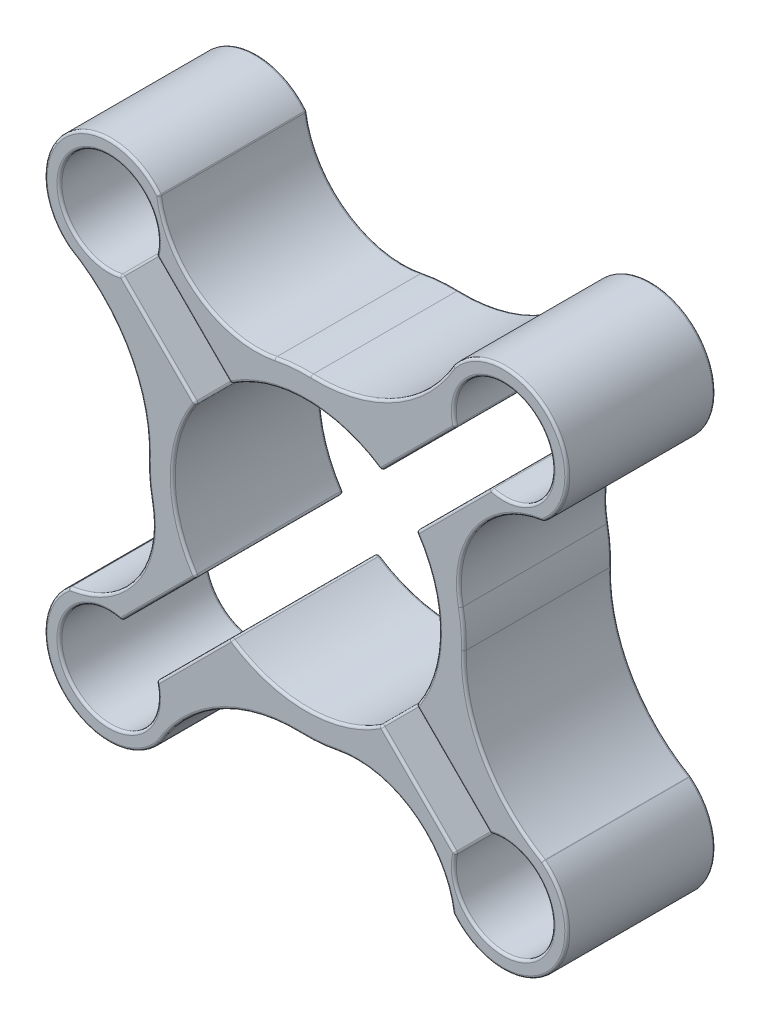
SolidWorks part; units mm, degrees
ref_plane "Front Plane" through (0, 0, 0) normal (0, 0, 1) x (1, 0, 0)
ref_plane "Top Plane" through (0, 0, 0) normal (0, 1, 0) x (1, 0, 0)
ref_plane "Right Plane" through (0, 0, 0) normal (1, 0, 0) x (0, 0, -1)
sketch "Sketch1" plane through (0, 0, 0) normal (0, 0, 1) x (1, 0, 0)
  line L0 (0, 0) -> (0, -51885.6815) construction
  line L1 (0, 0) -> (-51885.6815, 0) construction
  line L2 (707.1068, 707.1068) -> (0, 0) construction
  line L3 (30.2923, 37.3633) -> (15.2261, 22.2972)
  line L4 (37.3633, 30.2923) -> (22.2972, 15.2261)
  line L5 (37.3633, -30.2923) -> (22.2972, -15.2261)
  line L6 (30.2923, -37.3633) -> (15.2261, -22.2972)
  line L7 (-30.2923, -37.3633) -> (-15.2261, -22.2972)
  line L8 (-37.3633, -30.2923) -> (-22.2972, -15.2261)
  line L9 (-37.3633, 30.2923) -> (-22.2972, 15.2261)
  line L10 (-30.2923, 37.3633) -> (-15.2261, 22.2972)
  circle A0 centre (0, 0) radius 56.5 construction
  arc A1 (-31.9841, 1.0085) -> (-31.3676, -6.3304) centre (0, 0) ccw
  arc A2 (37.3633, 30.2923) -> (30.2923, 37.3633) centre (39.9515, 39.9515) ccw
  arc A4 (-22.2972, 15.2261) -> (-22.2972, -15.2261) centre (0, 0) ccw
  arc A5 (30.2923, -37.3633) -> (37.3633, -30.2923) centre (39.9515, -39.9515) ccw
  arc A7 (-37.3633, -30.2923) -> (-30.2923, -37.3633) centre (-39.9515, -39.9515) ccw
  arc A9 (-30.2923, 37.3633) -> (-37.3633, 30.2923) centre (-39.9515, 39.9515) ccw
  arc A10 (-29.7626, 48.0254) -> (-6.3304, 31.3676) centre (-10.2302, 50.6916) ccw
  arc A11 (15.2261, 22.2972) -> (-15.2261, 22.2972) centre (0, 0) ccw
  arc A12 (1.0085, 31.9841) -> (-6.3304, 31.3676) centre (0, 0) ccw
  arc A13 (-1.0085, -31.9841) -> (6.3304, -31.3676) centre (0, 0) ccw
  arc A14 (-15.2261, -22.2972) -> (15.2261, -22.2972) centre (0, 0) ccw
  arc A15 (22.2972, -15.2261) -> (22.2972, 15.2261) centre (0, 0) ccw
  arc A16 (31.9841, -1.0085) -> (31.3676, 6.3304) centre (0, 0) ccw
  arc A17 (29.7626, 48.0254) -> (1.0085, 31.9841) centre (2.0169, 63.9682) cw
  arc A18 (-29.7626, 48.0254) -> (-48.0254, 29.7626) centre (-39.9515, 39.9515) ccw
  arc A19 (48.0254, 29.7626) -> (29.7626, 48.0254) centre (39.9515, 39.9515) ccw
  arc A20 (-48.0254, 29.7626) -> (-31.9841, 1.0085) centre (-63.9682, 2.0169) cw
  arc A22 (48.0254, 29.7626) -> (31.3676, 6.3304) centre (50.6916, 10.2302) ccw
  arc A23 (48.0254, -29.7626) -> (31.9841, -1.0085) centre (63.9682, -2.0169) cw
  arc A24 (29.7626, -48.0254) -> (48.0254, -29.7626) centre (39.9515, -39.9515) ccw
  arc A25 (29.7626, -48.0254) -> (6.3304, -31.3676) centre (10.2302, -50.6916) ccw
  arc A26 (-29.7626, -48.0254) -> (-1.0085, -31.9841) centre (-2.0169, -63.9682) cw
  arc A27 (-48.0254, -29.7626) -> (-29.7626, -48.0254) centre (-39.9515, -39.9515) ccw
  arc A28 (-48.0254, -29.7626) -> (-31.3676, -6.3304) centre (-50.6916, -10.2302) ccw
  point P41 (0, 0)
  point P74 (0, 0)
  dimension "D1" = 113
  dimension "D2" = 64
  dimension "D4" = 20
  dimension "D7" = 54
  dimension "D9" = 19.7136
  dimension "D10" = 32
  dimension "D11" = 13
  dimension "D12" = 4
  dimension "D3" = 45
  dimension "D6" = 10
  dimension "D8" = 4
extrude "Boss-Extrude1" add sketch "Sketch1" along normal mid plane 30
fillet "Fillet1" radius 0.5 88 edges at (-48.0254, -29.7626, 0) (-29.7626, -48.0254, 0) (29.7626, -48.0254, 0) (48.0254, -29.7626, 0) (48.0254, 29.7626, 0) (29.7626, 48.0254, 0) (-29.7626, 48.0254, 0) (-48.0254, 29.7626, 0) (-49.1439, 49.1439, 15) (-21.6523, 34.6242, 15) (-2.6787, 31.8877, 15) (17.607, 36.0227, 15) (49.1439, 49.1439, 15) (34.6242, 21.6523, 15) (31.8877, 2.6787, 15) (36.0227, -17.607, 15) (49.1439, -49.1439, 15) (21.6523, -34.6242, 15) (2.6787, -31.8877, 15) (-17.607, -36.0227, 15) (-49.1439, -49.1439, 15) (-34.6242, -21.6523, 15) (-31.8877, -2.6787, 15) (-36.0227, 17.607, 15) (-49.1439, 49.1439, -15) (-21.6523, 34.6242, -15) (-2.6787, 31.8877, -15) (17.607, 36.0227, -15) (49.1439, 49.1439, -15) (34.6242, 21.6523, -15) (31.8877, 2.6787, -15) (36.0227, -17.607, -15) (49.1439, -49.1439, -15) (21.6523, -34.6242, -15) (2.6787, -31.8877, -15) (-17.607, -36.0227, -15) (-49.1439, -49.1439, -15) (-34.6242, -21.6523, -15) (-31.8877, -2.6787, -15) (-36.0227, 17.607, -15) (30.2923, 37.3633, 0) (15.2261, 22.2972, 0) (-15.2261, 22.2972, 0) (-30.2923, 37.3633, 0) (-37.3633, 30.2923, 0) (-22.2972, 15.2261, 0) (-22.2972, -15.2261, 0) (-37.3633, -30.2923, 0) (-30.2923, -37.3633, 0) (-15.2261, -22.2972, 0) (15.2261, -22.2972, 0) (30.2923, -37.3633, 0) (37.3633, -30.2923, 0) (22.2972, -15.2261, 0) (22.2972, 15.2261, 0) (37.3633, 30.2923, 0) (29.8303, 22.7592, 15) (27, 0, 15) (29.8303, -22.7592, 15) (47.0226, -47.0226, 15) (22.7592, -29.8303, 15) (0, -27, 15) (-22.7592, -29.8303, 15) (-47.0226, -47.0226, 15) (-29.8303, -22.7592, 15) (-27, 0, 15) (-29.8303, 22.7592, 15) (-47.0226, 47.0226, 15) (-22.7592, 29.8303, 15) (0, 27, 15) (22.7592, 29.8303, 15) (47.0226, 47.0226, 15) (29.8303, 22.7592, -15) (27, 0, -15) (29.8303, -22.7592, -15) (47.0226, -47.0226, -15) (22.7592, -29.8303, -15) (0, -27, -15) (-22.7592, -29.8303, -15) (-47.0226, -47.0226, -15) (-29.8303, -22.7592, -15) (-27, 0, -15) (-29.8303, 22.7592, -15) (-47.0226, 47.0226, -15) (-22.7592, 29.8303, -15) (0, 27, -15) (22.7592, 29.8303, -15) (47.0226, 47.0226, -15)
